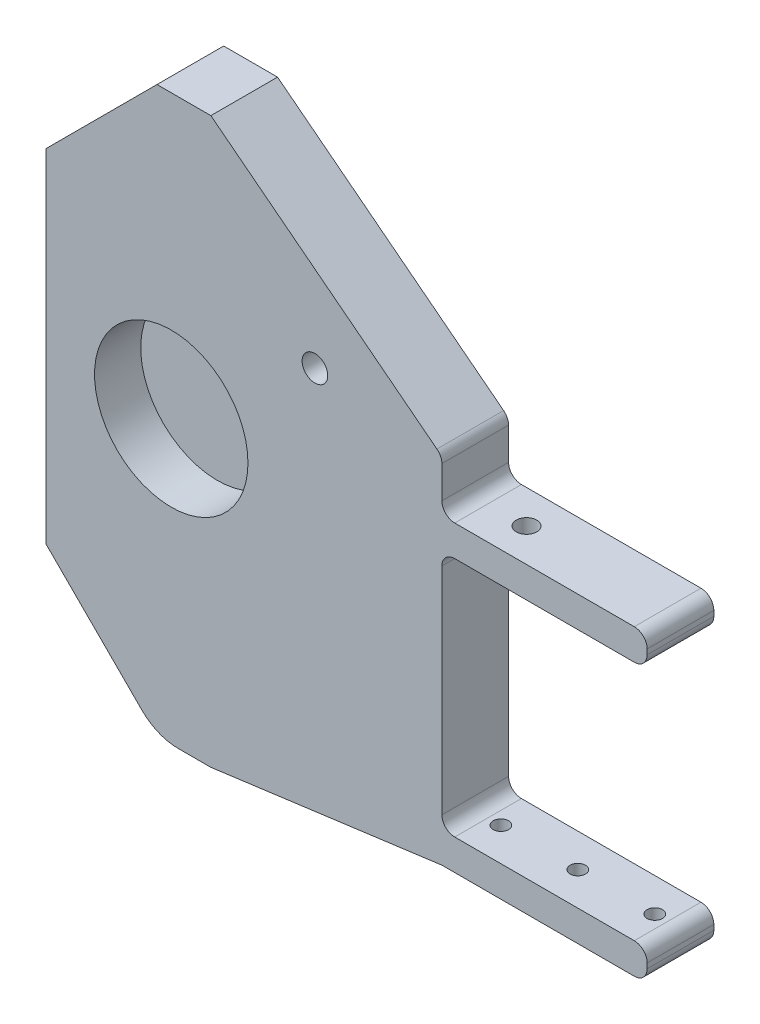
SolidWorks part; units mm, degrees
material "5052-H36"
ref_plane "Plano frontal" through (0, 0, 0) normal (0, 0, 1) x (1, 0, 0)
ref_plane "Plano superior" through (0, 0, 0) normal (0, 1, 0) x (1, 0, 0)
ref_plane "Plano direito" through (0, 0, 0) normal (1, 0, 0) x (0, 0, -1)
sketch "Esboço1" plane through (0, 0, 0) normal (0, 0, 1) x (1, 0, 0)
  line L0 (79.1281, 0) -> (0, 0) construction
  line L3 (4.9801, 55) -> (32.742, 55)
  line L6 (32.742, 55) -> (-22.7817, 55)
  line L12 (-22.7817, 55) -> (-44.3754, 33.4063)
  line L14 (-44.3754, -33.4063) -> (-22.7817, -55)
  line L15 (-22.7817, -55) -> (32.742, -55)
  line L18 (393.8557, 316.0739) -> (396.402, 318.6203) [skipped]
  line L19 (55, 501.996) -> (55, 520.8093) [skipped]
  line L20 (-316.0739, 393.8557) -> (-318.6203, 396.402) [skipped]
  line L21 (32.742, 55) -> (32.742, 10)
  line L22 (32.742, -49) -> (32.742, -55)
  line L23 (32.742, -49) -> (72.742, -49)
  line L25 (32.742, -43) -> (72.742, -43)
  line L26 (72.742, -49) -> (72.742, -43)
  line L27 (32.742, 4) -> (32.742, -43)
  line L28 (32.742, 4) -> (72.742, 4)
  line L30 (32.742, 10) -> (72.742, 10)
  line L31 (72.742, 4) -> (72.742, 10)
  line L32 (-44.3754, 33.4063) -> (-44.3754, -33.4063)
  line L34 (-55, 7.7563) -> (-55, -6.3461) [skipped]
  circle A0 centre (0, 0) radius 15 construction
  arc A3 (4.9801, 55) -> (0, -55.225) centre (0, 0) ccw construction
  point P14 (4.9801, 55)
  dimension "D1" = 30
  dimension "D5" = 110
  dimension "D6" = 40
  dimension "D7" = 6
  dimension "D8" = 6
  dimension "D9" = 45
extrude "Ressalto-extrusão1" add sketch "Esboço1" along normal mid plane 13 contours L14 L15 L3 L6 L12 A0 region at (-0.7875, -1.1016, 0)
sketch "Esboço2" plane through (0, 0, 6.5) normal (0, 0, 1) x (1, 0, 0)
  circle A1 centre (-20, 0) radius 14.95
  dimension "D1" = 29.9
  dimension "D2" = 20
extrude "Corte-extrusão1" cut sketch "Esboço2" against normal blind 9
sketch "Esboço3" plane through (0, 0, 6.5) normal (0, 0, 1) x (1, 0, 0)
  line L0 (-22.7817, -55) -> (32.742, -55) construction
  line L1 (-12.2817, -55) -> (32.742, -49)
  line L2 (32.742, -49) -> (32.742, -55)
  line L3 (32.742, -55) -> (-12.2817, -55)
  line L4 (-12.2817, -55) -> (-12.2817, 66.3095) construction
  line L6 (32.742, 10) -> (72.742, 10) construction
  line L11 (32.742, 55) -> (-12.2817, 55)
  line L12 (-12.2817, 55) -> (32.742, 20)
  line L13 (32.742, 20) -> (32.742, 55)
  circle A0 centre (8, 22.5) radius 2.5
  point P0 (-12.2817, -55)
  dimension "D2" = 5
  dimension "D1" = 10.5
  dimension "D3" = 22.5
  dimension "D4" = 28
  dimension "D5" = 10
extrude "Corte-extrusão2" cut sketch "Esboço3" against normal blind 13
fillet "Filete1" radius 10 1 edges at (-22.7817, -55, 0)
sketch "Esboço4" plane through (0, 0, -6.5) normal (0, 0, -1) x (-1, 0, 0)
  line L0 (44.3754, 33.4063) -> (44.3754, -33.4063) construction
  circle A0 centre (36.3754, 8.4063) radius 2
  circle A1 centre (12.9554, -16.5937) radius 2
  circle A2 centre (22.3754, -27.5937) radius 2
  dimension "D1" = 4
  dimension "D2" = 25
  dimension "D3" = 8
  dimension "D4" = 23.42
  dimension "D5" = 25
  dimension "D6" = 36
  dimension "D7" = 14
extrude "Corte-extrusão3" cut sketch "Esboço4" against normal blind 10
sketch "Esboço6" plane through (0, 10, 0) normal (0, 1, 0) x (1, 0, 0)
  circle A0 centre (42.742, -0.0016) radius 2
  circle A1 centre (45.5551, -19.8028) radius 2
  circle A2 centre (42.742, -0.0016) radius 2 construction
  dimension "D1" = 20
extrude "Corte-extrusão4" cut sketch "Esboço6" against normal blind 10
sketch "Esboço7" plane through (0, -49, 0) normal (0, -1, 0) x (1, 0, 0)
  line L0 (32.742, -6.5) -> (72.742, -6.5) construction
  line L1 (37.742, 0) -> (67.742, 0) construction
  line L2 (72.742, 6.5) -> (72.742, -6.5) construction
  circle A0 centre (37.742, 0) radius 1.5
  circle A1 centre (52.742, 0) radius 1.5
  circle A2 centre (67.742, 0) radius 1.5
  dimension "D1" = 3
  dimension "D2" = 6.5
  dimension "D3" = 5
  dimension "D4" = 20
  dimension "D5" = 35
extrude "Corte-extrusão5" cut sketch "Esboço7" against normal blind 10
fillet "Filete2" radius 2.5 8 edges at (72.742, -49, 0) (72.742, -43, 0) (72.742, 4, 0) (72.742, 10, 0) (32.742, 20, 0) (32.742, -43, 0) (32.742, 10, 0) (32.742, 4, 0)
